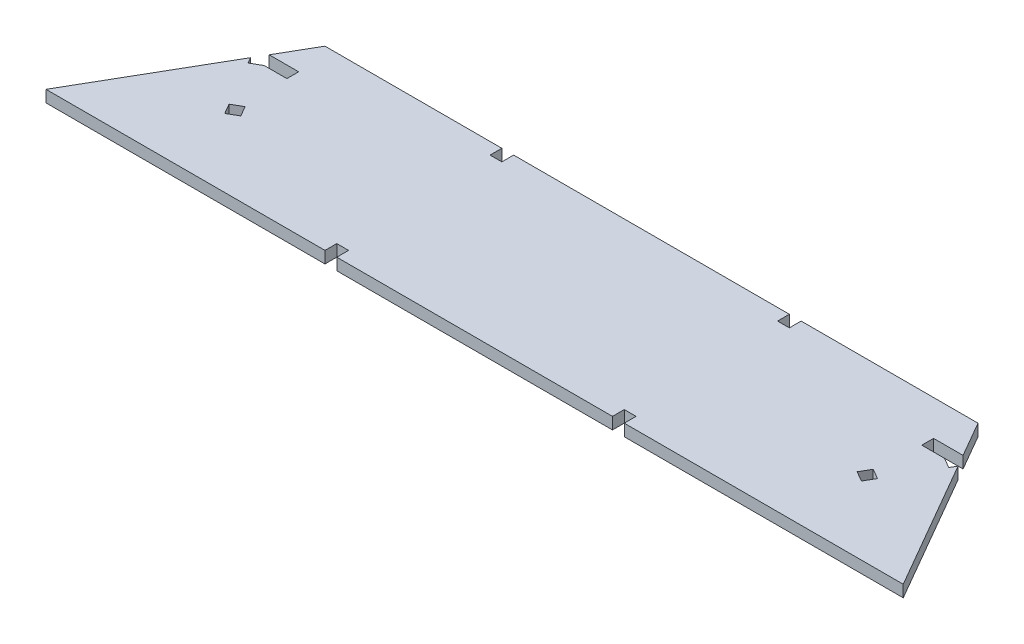
SolidWorks part; units mm, degrees
material "Plywood"
ref_plane "Front Plane" through (0, 0, 0) normal (0, 0, 1) x (1, 0, 0)
ref_plane "Top Plane" through (0, 0, 0) normal (0, 1, 0) x (1, 0, 0)
ref_plane "Right Plane" through (0, 0, 0) normal (1, 0, 0) x (0, 0, -1)
sketch "Sketch1" plane through (0, 609.6, 0) normal (0, 1, 0) x (1, 0, 0)
  line L12 (923.3117, 0) -> (461.6558, 799.6114)
  line L13 (461.6558, 799.6114) -> (-461.6558, 799.6114)
  line L14 (-461.6558, 799.6114) -> (-923.3117, 0)
  line L15 (-923.3117, 0) -> (-461.6558, -799.6114)
  line L16 (-461.6558, -799.6114) -> (461.6558, -799.6114)
  line L17 (461.6558, -799.6114) -> (923.3117, 0)
  line L18 (923.3117, 0) -> (461.6558, 799.6114)
  line L19 (461.6558, 799.6114) -> (-461.6558, 799.6114)
  line L20 (-461.6558, 799.6114) -> (-923.3117, 0)
  line L21 (-923.3117, 0) -> (-461.6558, -799.6114)
  line L22 (-461.6558, -799.6114) -> (461.6558, -799.6114)
  line L23 (461.6558, -799.6114) -> (923.3117, 0)
  line L24 (-351.6706, 609.1114) -> (-703.3412, 0)
  line L25 (-703.3412, 0) -> (-351.6706, -609.1114)
  line L26 (-351.6706, -609.1114) -> (351.6706, -609.1114)
  line L27 (351.6706, -609.1114) -> (703.3412, 0)
  line L28 (703.3412, 0) -> (351.6706, 609.1114)
  line L29 (351.6706, 609.1114) -> (-351.6706, 609.1114)
  line L30 (-351.6706, 609.1114) -> (-703.3412, 0)
  line L31 (-703.3412, 0) -> (-351.6706, -609.1114)
  line L32 (-351.6706, -609.1114) -> (351.6706, -609.1114)
  line L33 (351.6706, -609.1114) -> (703.3412, 0)
  line L34 (703.3412, 0) -> (351.6706, 609.1114)
  line L35 (351.6706, 609.1114) -> (-351.6706, 609.1114)
  dimension "D1" = 0
  dimension "D2" = 0
extrude "Boss-Extrude1" add sketch "Sketch1" against normal blind 12.7
sketch "Sketch2" plane through (0, 609.6, 0) normal (0, 1, 0) x (1, 0, 0)
  line L0 (-351.6706, -609.1114) -> (-461.6558, -799.6114)
  line L1 (-461.6558, -799.6114) -> (461.6558, -799.6114)
  line L2 (461.6558, -799.6114) -> (351.6706, -609.1114)
  line L3 (351.6706, -609.1114) -> (-351.6706, -609.1114)
extrude "Cut-Extrude1" cut sketch "Sketch2" against normal up to vertex (12.7 mm away) flip side to cut up to point (-461.6558, 596.9, 799.6114)
sketch "Sketch3" plane through (0, 609.6, 0) normal (0, 1, 0) x (1, 0, 0)
  line L3040 (-148.4706, -609.1114) -> (-161.1706, -609.1114)
  line L3041 (-148.4706, -621.8114) -> (-148.4706, -609.1114)
  line L3042 (-161.1706, -621.8114) -> (-148.4706, -621.8114)
  line L3043 (-161.1706, -609.1114) -> (-161.1706, -621.8114)
  line L3044 (-148.4706, -609.1114) -> (-161.1706, -609.1114)
  line L3045 (-148.4706, -621.8114) -> (-148.4706, -609.1114)
  line L3046 (-161.1706, -621.8114) -> (-148.4706, -621.8114)
  line L3047 (-161.1706, -609.1114) -> (-161.1706, -621.8114)
  line L3048 (-342.9, -725.9025) -> (-331.9015, -719.5525)
  line L3049 (-331.9015, -719.5525) -> (-338.2515, -708.554)
  line L3050 (-338.2515, -708.554) -> (-349.25, -714.904)
  line L3051 (-349.25, -714.904) -> (-342.9, -725.9025)
  line L3052 (-342.9, -725.9025) -> (-331.9015, -719.5525)
  line L3053 (-331.9015, -719.5525) -> (-338.2515, -708.554)
  line L3054 (-338.2515, -708.554) -> (-349.25, -714.904)
  line L3055 (-349.25, -714.904) -> (-342.9, -725.9025)
  line L3056 (-148.4706, -786.9114) -> (-161.1706, -786.9114)
  line L3057 (-148.4706, -799.6114) -> (-148.4706, -786.9114)
  line L3058 (-161.1706, -799.6114) -> (-148.4706, -799.6114)
  line L3059 (-161.1706, -786.9114) -> (-161.1706, -799.6114)
  line L3060 (-148.4706, -786.9114) -> (-161.1706, -786.9114)
  line L3061 (-148.4706, -799.6114) -> (-148.4706, -786.9114)
  line L3062 (-161.1706, -799.6114) -> (-148.4706, -799.6114)
  line L3063 (-161.1706, -786.9114) -> (-161.1706, -799.6114)
  line L3064 (-373.6677, -647.2114) -> (-381, -659.9114)
  line L3065 (-381, -659.9114) -> (-377.3338, -666.2614)
  line L3066 (-377.3338, -666.2614) -> (-366.3353, -659.9114)
  line L3067 (-366.3353, -659.9114) -> (-373.6677, -647.2114)
  line L3068 (-373.6677, -647.2114) -> (-381, -659.9114)
  line L3069 (-381, -659.9114) -> (-377.3338, -666.2614)
  line L3070 (-377.3338, -666.2614) -> (-366.3353, -659.9114)
  line L3071 (-366.3353, -659.9114) -> (-373.6677, -647.2114)
  line L3072 (381, -659.9114) -> (373.6677, -647.2114)
  line L3073 (373.6677, -647.2114) -> (366.3353, -659.9114)
  line L3074 (366.3353, -659.9114) -> (377.3338, -666.2614)
  line L3075 (377.3338, -666.2614) -> (381, -659.9114)
  line L3076 (381, -659.9114) -> (373.6677, -647.2114)
  line L3077 (373.6677, -647.2114) -> (366.3353, -659.9114)
  line L3078 (366.3353, -659.9114) -> (377.3338, -666.2614)
  line L3079 (377.3338, -666.2614) -> (381, -659.9114)
  line L3080 (338.2515, -708.554) -> (331.9015, -719.5525)
  line L3081 (349.25, -714.904) -> (338.2515, -708.554)
  line L3082 (342.9, -725.9025) -> (349.25, -714.904)
  line L3083 (331.9015, -719.5525) -> (342.9, -725.9025)
  line L3084 (338.2515, -708.554) -> (331.9015, -719.5525)
  line L3085 (349.25, -714.904) -> (338.2515, -708.554)
  line L3086 (342.9, -725.9025) -> (349.25, -714.904)
  line L3087 (331.9015, -719.5525) -> (342.9, -725.9025)
  line L3088 (148.4706, -621.8114) -> (161.1706, -621.8114)
  line L3089 (148.4706, -609.1114) -> (148.4706, -621.8114)
  line L3090 (161.1706, -609.1114) -> (148.4706, -609.1114)
  line L3091 (161.1706, -621.8114) -> (161.1706, -609.1114)
  line L3092 (148.4706, -621.8114) -> (161.1706, -621.8114)
  line L3093 (148.4706, -609.1114) -> (148.4706, -621.8114)
  line L3094 (161.1706, -609.1114) -> (148.4706, -609.1114)
  line L3095 (161.1706, -621.8114) -> (161.1706, -609.1114)
  line L3096 (161.1706, -786.9114) -> (148.4706, -786.9114)
  line L3097 (161.1706, -799.6114) -> (161.1706, -786.9114)
  line L3098 (148.4706, -799.6114) -> (161.1706, -799.6114)
  line L3099 (148.4706, -786.9114) -> (148.4706, -799.6114)
  line L3100 (161.1706, -786.9114) -> (148.4706, -786.9114)
  line L3101 (161.1706, -799.6114) -> (161.1706, -786.9114)
  line L3102 (148.4706, -799.6114) -> (161.1706, -799.6114)
  line L3103 (148.4706, -786.9114) -> (148.4706, -799.6114)
  dimension "D1" = 0
  dimension "D2" = 0
  dimension "D3" = 0
  dimension "D4" = 0
  dimension "D5" = 0
  dimension "D6" = 0
  dimension "D7" = 0
  dimension "D8" = 0
extrude "Cut-Extrude2" cut sketch "Sketch3" against normal up to vertex (12.7 mm away) up to point (-461.6558, 596.9, 799.6114)
sketch "Sketch4" plane through (0, 609.6, 0) normal (0, 1, 0) x (1, 0, 0)
  line L0 (-373.6677, -647.2114) -> (-341.9177, -647.2114)
  line L1 (-341.9177, -647.2114) -> (-341.9177, -659.9114)
  line L2 (-341.9177, -659.9114) -> (-366.3353, -659.9114)
  line L3 (-366.3353, -659.9114) -> (-373.6677, -647.2114)
  line L4 (0, -609.1114) -> (0, -799.6114) construction
  line L11 (-148.4706, -609.1114) -> (148.4706, -609.1114) construction
  line L12 (-148.4706, -799.6114) -> (148.4706, -799.6114) construction
  line L13 (341.9177, -659.9114) -> (366.3353, -659.9114)
  line L14 (341.9177, -647.2114) -> (341.9177, -659.9114)
  line L15 (373.6677, -647.2114) -> (341.9177, -647.2114)
  line L16 (366.3353, -659.9114) -> (373.6677, -647.2114)
  dimension "D1" = 31.75
extrude "Cut-Extrude3" cut sketch "Sketch4" against normal up to vertex (12.7 mm away) contours L13 | L0 L1 L2 L3 region at (356.0393, 609.6, 653.285) up to point (-461.6558, 596.9, 799.6114)
